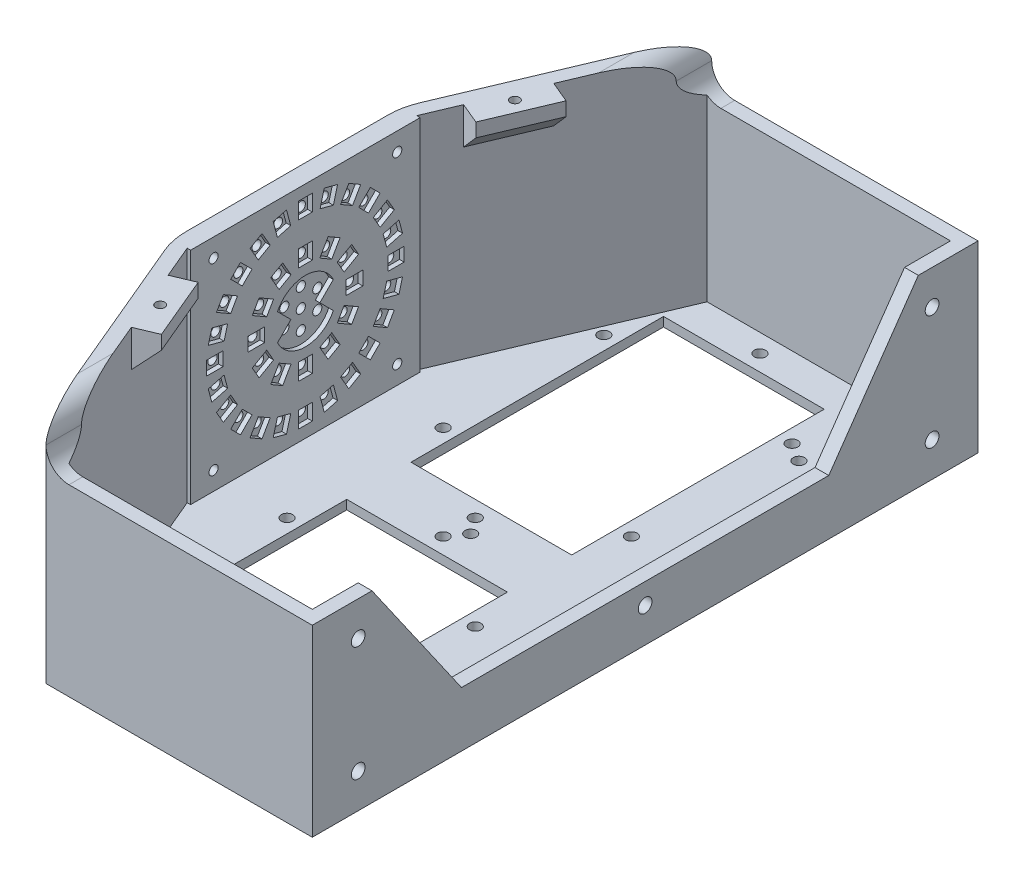
SolidWorks part; units mm, degrees
ref_plane "Спереди" through (0, 0, 0) normal (0, 0, 1) x (1, 0, 0)
ref_plane "Сверху" through (0, 0, 0) normal (0, 1, 0) x (1, 0, 0)
ref_plane "Справа" through (0, 0, 0) normal (1, 0, 0) x (0, 0, -1)
sketch "Эскиз1" plane through (0, 0, 0) normal (0, 1, 0) x (1, 0, 0)
  line L0 (0, 159.887) -> (0, 0) construction
  line L1 (0, 0) -> (281.7797, 0) construction
  line L2 (-95, -50) -> (-95, 50)
  line L3 (-55, -145) -> (55, -145)
  line L5 (-55, 145) -> (55, 145)
  line L6 (55, -145) -> (55, 145)
  line L7 (0, 145) -> (0, -145) construction
  line L8 (-435.8276, 0) -> (55, 0) construction
  line L9 (-95, 50) -> (-55, 145)
  line L10 (-95, -50) -> (-55, -145)
  point P10 (-95, 0)
  dimension "D1" = 290
  dimension "D2" = 110
  dimension "D3" = 100
  dimension "D4" = 150
extrude "Бобышка-Вытянуть1" add sketch "Эскиз1" along normal blind 4
sketch "Эскиз2" plane through (0, 0, 0) normal (0, 1, 0) x (1, 0, 0)
  line L1 (55, 145) -> (61, 145)
  line L2 (55, 145) -> (55, -145)
  line L3 (55, -145) -> (61, -145)
  line L4 (61, 145) -> (61, -145)
  dimension "D1" = 290
  dimension "D2" = 6
extrude "Бобышка-Вытянуть2" add sketch "Эскиз2" along normal blind 80
sketch "Эскиз17" plane through (0, 4, 0) normal (0, 1, 0) x (1, 0, 0)
  line L0 (-55, 145) -> (-95, 50)
  line L1 (-95, 50) -> (-95, -50)
  line L2 (-95, -50) -> (-55, -145)
  line L3 (-55, -145) -> (61, -145)
  line L4 (61, -145) -> (61, 145)
  line L5 (61, 145) -> (-55, 145)
extrude "Вытянуть-Тонкостенный1" add sketch "Эскиз17" along normal blind 96 thin thin type one direction reverse wall 6
sketch "Эскиз29" plane through (0, 100, 0) normal (0, 1, 0) x (1, 0, 0)
  line L1 (-95, 50) -> (-87, 50)
  line L2 (-95, 50) -> (-95, -50)
  line L3 (-95, -50) -> (-87, -50)
  line L4 (-87, 50) -> (-87, -50)
  dimension "D1" = 8
extrude "Бобышка-Вытянуть5" add sketch "Эскиз29" against normal blind 96
sketch "Эскиз20" plane through (-87, 0, 0) normal (1, 0, 0) x (0, 0, -1)
  line L0 (8.2314, 94.3113) -> (6.3873, 87.4288)
  line L1 (6.3, 52) -> (12.1612, 57.8612)
  line L10 (0, 0) -> (0, 100) construction
  line L12 (-48.7884, 52) -> (48.7884, 52) construction
  line L15 (-3, 95) -> (3, 95)
  line L16 (-3, 95) -> (-3, 87.8748)
  line L17 (-3, 87.8748) -> (3, 87.8748)
  line L18 (3, 95) -> (3, 87.8748)
  line L19 (0, 87.8748) -> (0, 95) construction
  line L20 (-3, 91.4374) -> (3, 91.4374) construction
  line L21 (8.2314, 94.3113) -> (14.027, 92.7584)
  line L22 (14.027, 92.7584) -> (12.1829, 85.8759)
  line L23 (6.3873, 87.4288) -> (12.1829, 85.8759)
  line L24 (18.9019, 90.7391) -> (15.3393, 84.5685)
  line L25 (18.9019, 90.7391) -> (24.0981, 87.7391)
  line L26 (24.0981, 87.7391) -> (20.5355, 81.5685)
  line L27 (15.3393, 84.5685) -> (20.5355, 81.5685)
  line L28 (28.2843, 84.5269) -> (23.246, 79.4886)
  line L29 (28.2843, 84.5269) -> (32.5269, 80.2843)
  line L30 (32.5269, 80.2843) -> (27.4886, 75.246)
  line L31 (23.246, 79.4886) -> (27.4886, 75.246)
  line L32 (35.7391, 76.0981) -> (29.5685, 72.5355)
  line L33 (35.7391, 76.0981) -> (38.7391, 70.9019)
  line L34 (38.7391, 70.9019) -> (32.5685, 67.3393)
  line L35 (29.5685, 72.5355) -> (32.5685, 67.3393)
  line L36 (40.7584, 66.027) -> (33.8759, 64.1829)
  line L37 (40.7584, 66.027) -> (42.3113, 60.2314)
  line L38 (42.3113, 60.2314) -> (35.4288, 58.3873)
  line L39 (33.8759, 64.1829) -> (35.4288, 58.3873)
  line L40 (43, 55) -> (35.8748, 55)
  line L41 (43, 55) -> (43, 49)
  line L42 (43, 49) -> (35.8748, 49)
  line L43 (35.8748, 55) -> (35.8748, 49)
  line L44 (42.3113, 43.7686) -> (35.4288, 45.6127)
  line L45 (42.3113, 43.7686) -> (40.7584, 37.973)
  line L46 (40.7584, 37.973) -> (33.8759, 39.8171)
  line L47 (35.4288, 45.6127) -> (33.8759, 39.8171)
  line L48 (38.7391, 33.0981) -> (32.5685, 36.6607)
  line L49 (38.7391, 33.0981) -> (35.7391, 27.9019)
  line L50 (35.7391, 27.9019) -> (29.5685, 31.4645)
  line L51 (32.5685, 36.6607) -> (29.5685, 31.4645)
  line L52 (32.5269, 23.7157) -> (27.4886, 28.754)
  line L53 (32.5269, 23.7157) -> (28.2843, 19.4731)
  line L54 (28.2843, 19.4731) -> (23.246, 24.5114)
  line L55 (27.4886, 28.754) -> (23.246, 24.5114)
  line L56 (24.0981, 16.2609) -> (20.5355, 22.4315)
  line L57 (24.0981, 16.2609) -> (18.9019, 13.2609)
  line L58 (18.9019, 13.2609) -> (15.3393, 19.4315)
  line L59 (20.5355, 22.4315) -> (15.3393, 19.4315)
  line L60 (14.027, 11.2416) -> (12.1829, 18.1241)
  line L61 (14.027, 11.2416) -> (8.2314, 9.6887)
  line L62 (8.2314, 9.6887) -> (6.3873, 16.5712)
  line L63 (12.1829, 18.1241) -> (6.3873, 16.5712)
  line L64 (3, 9) -> (3, 16.1252)
  line L65 (3, 9) -> (-3, 9)
  line L66 (-3, 9) -> (-3, 16.1252)
  line L67 (3, 16.1252) -> (-3, 16.1252)
  line L68 (-8.2314, 9.6887) -> (-6.3873, 16.5712)
  line L69 (-8.2314, 9.6887) -> (-14.027, 11.2416)
  line L70 (-14.027, 11.2416) -> (-12.1829, 18.1241)
  line L71 (-6.3873, 16.5712) -> (-12.1829, 18.1241)
  line L72 (-18.9019, 13.2609) -> (-15.3393, 19.4315)
  line L73 (-18.9019, 13.2609) -> (-24.0981, 16.2609)
  line L74 (-24.0981, 16.2609) -> (-20.5355, 22.4315)
  line L75 (-15.3393, 19.4315) -> (-20.5355, 22.4315)
  line L76 (-28.2843, 19.4731) -> (-23.246, 24.5114)
  line L77 (-28.2843, 19.4731) -> (-32.5269, 23.7157)
  line L78 (-32.5269, 23.7157) -> (-27.4886, 28.754)
  line L79 (-23.246, 24.5114) -> (-27.4886, 28.754)
  line L80 (-35.7391, 27.9019) -> (-29.5685, 31.4645)
  line L81 (-35.7391, 27.9019) -> (-38.7391, 33.0981)
  line L82 (-38.7391, 33.0981) -> (-32.5685, 36.6607)
  line L83 (-29.5685, 31.4645) -> (-32.5685, 36.6607)
  line L84 (-40.7584, 37.973) -> (-33.8759, 39.8171)
  line L85 (-40.7584, 37.973) -> (-42.3113, 43.7686)
  line L86 (-42.3113, 43.7686) -> (-35.4288, 45.6127)
  line L87 (-33.8759, 39.8171) -> (-35.4288, 45.6127)
  line L88 (-43, 49) -> (-35.8748, 49)
  line L89 (-43, 49) -> (-43, 55)
  line L90 (-43, 55) -> (-35.8748, 55)
  line L91 (-35.8748, 49) -> (-35.8748, 55)
  line L92 (-42.3113, 60.2314) -> (-35.4288, 58.3873)
  line L93 (-42.3113, 60.2314) -> (-40.7584, 66.027)
  line L94 (-40.7584, 66.027) -> (-33.8759, 64.1829)
  line L95 (-35.4288, 58.3873) -> (-33.8759, 64.1829)
  line L96 (-38.7391, 70.9019) -> (-32.5685, 67.3393)
  line L97 (-38.7391, 70.9019) -> (-35.7391, 76.0981)
  line L98 (-35.7391, 76.0981) -> (-29.5685, 72.5355)
  line L99 (-32.5685, 67.3393) -> (-29.5685, 72.5355)
  line L100 (-32.5269, 80.2843) -> (-27.4886, 75.246)
  line L101 (-32.5269, 80.2843) -> (-28.2843, 84.5269)
  line L102 (-28.2843, 84.5269) -> (-23.246, 79.4886)
  line L103 (-27.4886, 75.246) -> (-23.246, 79.4886)
  line L104 (-24.0981, 87.7391) -> (-20.5355, 81.5685)
  line L105 (-24.0981, 87.7391) -> (-18.9019, 90.7391)
  line L106 (-18.9019, 90.7391) -> (-15.3393, 84.5685)
  line L107 (-20.5355, 81.5685) -> (-15.3393, 84.5685)
  line L108 (-14.027, 92.7584) -> (-12.1829, 85.8759)
  line L109 (-14.027, 92.7584) -> (-8.2314, 94.3113)
  line L110 (-8.2314, 94.3113) -> (-6.3873, 87.4288)
  line L111 (-12.1829, 85.8759) -> (-6.3873, 87.4288)
  line L112 (6.276, 68.8704) -> (9.9019, 75.1506)
  line L113 (-3, 69.7482) -> (3, 69.7482)
  line L114 (-3, 69.7482) -> (-3, 77)
  line L115 (-3, 77) -> (3, 77)
  line L116 (3, 69.7482) -> (3, 77)
  line L117 (0, 77) -> (0, 69.7482) construction
  line L118 (-3, 73.3741) -> (3, 73.3741) construction
  line L119 (6.276, 68.8704) -> (11.4722, 65.8704)
  line L120 (11.4722, 65.8704) -> (15.0981, 72.1506)
  line L121 (9.9019, 75.1506) -> (15.0981, 72.1506)
  line L122 (13.8704, 63.4722) -> (20.1506, 67.0981)
  line L123 (13.8704, 63.4722) -> (16.8704, 58.276)
  line L124 (16.8704, 58.276) -> (23.1506, 61.9019)
  line L125 (20.1506, 67.0981) -> (23.1506, 61.9019)
  line L126 (17.7482, 55) -> (25, 55)
  line L127 (17.7482, 55) -> (17.7482, 49)
  line L128 (17.7482, 49) -> (25, 49)
  line L129 (25, 55) -> (25, 49)
  line L130 (16.8704, 45.724) -> (23.1506, 42.0981)
  line L131 (16.8704, 45.724) -> (13.8704, 40.5278)
  line L132 (13.8704, 40.5278) -> (20.1506, 36.9019)
  line L133 (23.1506, 42.0981) -> (20.1506, 36.9019)
  line L134 (11.4722, 38.1296) -> (15.0981, 31.8494)
  line L135 (11.4722, 38.1296) -> (6.276, 35.1296)
  line L136 (6.276, 35.1296) -> (9.9019, 28.8494)
  line L137 (15.0981, 31.8494) -> (9.9019, 28.8494)
  line L138 (3, 34.2518) -> (3, 27)
  line L139 (3, 34.2518) -> (-3, 34.2518)
  line L140 (-3, 34.2518) -> (-3, 27)
  line L141 (3, 27) -> (-3, 27)
  line L142 (-6.276, 35.1296) -> (-9.9019, 28.8494)
  line L143 (-6.276, 35.1296) -> (-11.4722, 38.1296)
  line L144 (-11.4722, 38.1296) -> (-15.0981, 31.8494)
  line L145 (-9.9019, 28.8494) -> (-15.0981, 31.8494)
  line L146 (-13.8704, 40.5278) -> (-20.1506, 36.9019)
  line L147 (-13.8704, 40.5278) -> (-16.8704, 45.724)
  line L148 (-16.8704, 45.724) -> (-23.1506, 42.0981)
  line L149 (-20.1506, 36.9019) -> (-23.1506, 42.0981)
  line L150 (-17.7482, 49) -> (-25, 49)
  line L151 (-17.7482, 49) -> (-17.7482, 55)
  line L152 (-17.7482, 55) -> (-25, 55)
  line L153 (-25, 49) -> (-25, 55)
  line L154 (-16.8704, 58.276) -> (-23.1506, 61.9019)
  line L155 (-16.8704, 58.276) -> (-13.8704, 63.4722)
  line L156 (-13.8704, 63.4722) -> (-20.1506, 67.0981)
  line L157 (-23.1506, 61.9019) -> (-20.1506, 67.0981)
  line L158 (-11.4722, 65.8704) -> (-15.0981, 72.1506)
  line L159 (-11.4722, 65.8704) -> (-6.276, 68.8704)
  line L160 (-6.276, 68.8704) -> (-9.9019, 75.1506)
  line L161 (-15.0981, 72.1506) -> (-9.9019, 75.1506)
  line L162 (6.3, 52) -> (12.1612, 46.1388)
  line L163 (-6.3, 52) -> (-12.1612, 57.8612)
  line L164 (-6.3, 52) -> (-12.1612, 46.1388)
  circle A0 centre (0, 52) radius 36 construction
  circle A1 centre (0, 52) radius 43 construction
  circle A3 centre (0, 52) radius 25 construction
  circle A4 centre (0, 52) radius 18 construction
  circle A5 centre (0, 52) radius 13.5 construction
  arc A6 (-12.1612, 57.8612) -> (12.1612, 57.8612) centre (0, 52) cw
  arc A7 (-12.1612, 46.1388) -> (12.1612, 46.1388) centre (0, 52) ccw
  point P15 (0, 91.4374)
  point P21 (0, 73.3741)
  point P112 (0, 52)
  point P163 (0, 52)
  dimension "D1" = 72
  dimension "D2" = 86
  dimension "D3" = 50
  dimension "D5" = 36
  dimension "D7" = 27
  dimension "D4" = 6
  dimension "D6" = 6
  dimension "D8" = 6.3
  dimension "D9" = 90
extrude "Вырез-Вытянуть7" cut sketch "Эскиз20" against normal blind 2
sketch "Эскиз16" plane through (61, 0, 0) normal (1, 0, 0) x (0, 0, -1)
  line L0 (0, 111.0778) -> (0, 40) construction
  line L1 (0, 40) -> (205.7417, 40) construction
  line L2 (-145, 0) -> (145, 0) construction
  circle A0 centre (0, 65) radius 3
  circle A1 centre (0, 15) radius 3
  circle A2 centre (125, 65) radius 3
  circle A3 centre (-125, 65) radius 3
  circle A4 centre (-125, 15) radius 3
  circle A5 centre (125, 15) radius 3
  dimension "D2" = 6
  dimension "D3" = 25
  dimension "D4" = 125
  dimension "D1" = 40
extrude "Вырез-Вытянуть6" cut sketch "Эскиз16" against normal blind 20
sketch "Эскиз21" plane through (-87, 0, 0) normal (1, 0, 0) x (0, 0, -1)
  line L0 (48.7884, 52) -> (-48.7884, 52) construction
  line L3 (0, 100) -> (0, 0) construction
  circle A0 centre (0, 52) radius 38.5 construction
  circle A1 centre (0, 90.5) radius 2
  circle A2 centre (9.9645, 89.1881) radius 2
  circle A3 centre (19.25, 85.342) radius 2
  circle A4 centre (27.2236, 79.2236) radius 2
  circle A5 centre (33.342, 71.25) radius 2
  circle A6 centre (37.1881, 61.9645) radius 2
  circle A7 centre (38.5, 52) radius 2
  circle A8 centre (37.1881, 42.0355) radius 2
  circle A9 centre (33.342, 32.75) radius 2
  circle A10 centre (27.2236, 24.7764) radius 2
  circle A11 centre (19.25, 18.658) radius 2
  circle A12 centre (9.9645, 14.8119) radius 2
  circle A13 centre (0, 13.5) radius 2
  circle A14 centre (-9.9645, 14.8119) radius 2
  circle A15 centre (-19.25, 18.658) radius 2
  circle A16 centre (-27.2236, 24.7764) radius 2
  circle A17 centre (-33.342, 32.75) radius 2
  circle A18 centre (-37.1881, 42.0355) radius 2
  circle A19 centre (-38.5, 52) radius 2
  circle A20 centre (-37.1881, 61.9645) radius 2
  circle A21 centre (-33.342, 71.25) radius 2
  circle A22 centre (-27.2236, 79.2236) radius 2
  circle A23 centre (-19.25, 85.342) radius 2
  circle A24 centre (-9.9645, 89.1881) radius 2
  circle A25 centre (0, 52) radius 21 construction
  circle A26 centre (0, 73) radius 2
  circle A27 centre (10.5, 70.1865) radius 2
  circle A28 centre (18.1865, 62.5) radius 2
  circle A29 centre (21, 52) radius 2
  circle A30 centre (18.1865, 41.5) radius 2
  circle A31 centre (10.5, 33.8135) radius 2
  circle A32 centre (0, 31) radius 2
  circle A33 centre (-10.5, 33.8135) radius 2
  circle A34 centre (-18.1865, 41.5) radius 2
  circle A35 centre (-21, 52) radius 2
  circle A36 centre (-18.1865, 62.5) radius 2
  circle A37 centre (-10.5, 70.1865) radius 2
  circle A38 centre (0, 52) radius 8.3 construction
  circle A39 centre (0, 60.3) radius 2
  circle A40 centre (7.188, 56.15) radius 2
  circle A41 centre (7.188, 47.85) radius 2
  circle A42 centre (0, 43.7) radius 2
  circle A43 centre (-7.188, 47.85) radius 2
  circle A44 centre (-7.188, 56.15) radius 2
  circle A45 centre (0, 52) radius 2
  point P64 (0, 52)
  point P90 (0, 52)
  point P104 (0, 52)
  dimension "D1" = 77
  dimension "D2" = 4
  dimension "D3" = 42
  dimension "D4" = 4
  dimension "D5" = 16.6
  dimension "D6" = 4
extrude "Отверстия под LED" cut sketch "Эскиз21" against normal blind 10
sketch "Эскиз22" plane through (0, 100, 0) normal (0, 1, 0) x (1, 0, 0)
  line L1 (61, 145) -> (-55, 145)
  line L2 (61, 145) -> (61, -145)
  line L3 (61, -145) -> (-55, -145)
  line L4 (-55, 145) -> (-55, -145)
extrude "Вырез-Вытянуть9" cut sketch "Эскиз22" against normal blind 20
fillet "Скругление2" radius 10 4 edges at (-55, 100, -137.2692) (-55, 100, 137.2692) (-55, 80, -137.2692) (-55, 80, 137.2692)
fillet "Скругление3" radius 30 2 edges at (-95, 50, 50) (-95, 50, -50)
sketch "Эскиз23" plane through (-93.0467, 0, -39.1775) normal (0.9216, 0, 0.3881) x (0.3881, 0, -0.9216)
  line L0 (72.2746, 100) -> (11.7427, 100) construction
  line L1 (27.3208, 100) -> (57.3208, 100)
  line L2 (27.3208, 100) -> (27.3208, 94)
  line L3 (27.3208, 94) -> (57.3208, 94)
  line L4 (57.3208, 100) -> (57.3208, 94)
  line L6 (12.3208, 4) -> (12.3208, 100) construction
  dimension "D1" = 30
  dimension "D2" = 6
  dimension "D3" = 15
extrude "Бобышка-Вытянуть3" add sketch "Эскиз23" along normal blind 10
sketch "Эскиз24" plane through (-93.0467, 0, 39.1775) normal (0.9216, 0, -0.3881) x (-0.3881, 0, -0.9216)
  line L0 (-11.7427, 100) -> (-72.2746, 100) construction
  line L1 (-27.3208, 100) -> (-57.3208, 100)
  line L2 (-27.3208, 100) -> (-27.3208, 94)
  line L3 (-27.3208, 94) -> (-57.3208, 94)
  line L4 (-57.3208, 100) -> (-57.3208, 94)
  line L6 (-12.3208, 4) -> (-12.3208, 100) construction
  dimension "D1" = 30
  dimension "D2" = 6
  dimension "D3" = 15
extrude "Бобышка-Вытянуть4" add sketch "Эскиз24" along normal blind 10
chamfer "Фаска1" distance 10 angle 45 2 edges at (-76.6238, 94, -78.1819) (-76.6238, 94, 78.1819)
sketch "Эскиз27" plane through (61, 0, 0) normal (1, 0, 0) x (0, 0, -1)
  line L0 (-80, 24) -> (80, 24)
  line L1 (80, 24) -> (119, 80)
  line L2 (-145, 80) -> (145, 80) construction
  line L3 (119, 80) -> (-119, 80)
  line L4 (0, 118.8906) -> (0, 0) construction
  line L5 (-80, 24) -> (-119, 80)
  line L6 (-145, 0) -> (145, 0) construction
  line L7 (145, 80) -> (145, 0) construction
  point P10 (0, 80)
  point P11 (0, 24)
  dimension "D1" = 160
  dimension "D2" = 24
  dimension "D3" = 26
extrude "Вырез-Вытянуть10" cut sketch "Эскиз27" against normal blind 10
chamfer "Фаска2" distance 2 angle 45 24 edges at (-95, 71.25, 31.342) (-95, 61.9645, 35.1881) (-95, 52, 36.5) (-95, 42.0355, 35.1881) (-95, 32.75, 31.342) (-95, 24.7764, 25.2236) (-95, 18.658, 17.25) (-95, 14.8119, 7.9645) (-95, 13.5, -2) (-95, 14.8119, -11.9645) (-95, 18.658, -21.25) (-95, 24.7764, -29.2236) (-95, 32.75, -35.342) (-95, 42.0355, -39.1881) (-95, 52, -40.5) (-95, 61.9645, -39.1881) (-95, 71.25, -35.342) (-95, 79.2236, -29.2236) (-95, 85.342, -21.25) (-95, 89.1881, -11.9645) (-95, 90.5, -2) (-95, 79.2236, 25.2236) (-95, 85.342, 17.25) (-95, 89.1881, 7.9645)
sketch "Эскиз30" plane through (-87, 0, 0) normal (1, 0, 0) x (0, 0, -1)
  line L1 (-40, 12) -> (40, 12) construction
  line L2 (-40, 12) -> (-40, 92) construction
  line L3 (-40, 92) -> (40, 92) construction
  line L4 (40, 12) -> (40, 92) construction
  line L5 (0, 92) -> (0, 12) construction
  line L6 (-40, 52) -> (40, 52) construction
  circle A0 centre (-40, 92) radius 2
  circle A1 centre (40, 92) radius 2
  circle A2 centre (-40, 12) radius 2
  circle A3 centre (40, 12) radius 2
  point P0 (0, 52)
  dimension "D1" = 80
  dimension "D2" = 80
extrude "Вырез-Вытянуть11" cut sketch "Эскиз30" against normal blind 7
sketch "Эскиз32" plane through (0, 100, 0) normal (0, 1, 0) x (1, 0, 0)
  line L0 (-73, 139.8441) -> (-73, -154.1375) construction
  line L1 (-95, 43.9418) -> (-95, -43.9418) construction
  line L2 (0, 0) -> (-175.2904, 0) construction
  circle A0 centre (-73, 77.2619) radius 2
  circle A1 centre (-73, -77.2619) radius 2
  dimension "D2" = 77.2619
  dimension "D1" = 22
extrude "Вырез-Вытянуть13" cut sketch "Эскиз32" against normal blind 7
chamfer "Фаска3" distance 2 angle 45 7 edges at (-95, 47.85, 5.188) (-95, 43.7, -2) (-95, 47.85, -9.188) (-95, 56.15, -9.188) (-95, 52, -2) (-95, 56.15, 5.188) (-95, 60.3, -2)
sketch "Эскиз31" plane through (0, 100, 0) normal (0, 1, 0) x (1, 0, 0)
  line L1 (-70.4141, 145) -> (61, 145)
  line L2 (-70.4141, 145) -> (-70.4141, -145)
  line L3 (-70.4141, -145) -> (61, -145)
  line L4 (61, 145) -> (61, -145)
extrude "Вырез-Вытянуть12" [suppressed] cut sketch "Эскиз31" against normal blind 150
sketch "Эскиз33" plane through (0, 4, 0) normal (0, 1, 0) x (1, 0, 0)
  line L0 (-55, 124) -> (15, 124)
  line L1 (15, 124) -> (15, 14)
  line L2 (15, 14) -> (-55, 14)
  line L3 (-55, 14) -> (-55, 124)
  line L4 (0, 0) -> (-147.4761, 0) construction
  line L5 (55, 119) -> (55, 139) construction
  line L6 (55, 139) -> (-51.0161, 139) construction
  line L7 (15, -14) -> (-55, -14)
  line L8 (15, -124) -> (15, -14)
  line L9 (-55, -124) -> (15, -124)
  line L10 (-55, -14) -> (-55, -124)
  dimension "D1" = 40
  dimension "D2" = 70
  dimension "D3" = 110
  dimension "D4" = 15
extrude "Вырез-Вытянуть14" cut sketch "Эскиз33" against normal blind 10
sketch "Эскиз34" plane through (0, 4, 0) normal (0, 1, 0) x (1, 0, 0)
  line L0 (0, 0) -> (232.0731, 0) construction
  line L1 (-20, 157.0562) -> (-20, -124) construction
  line L3 (-55, -124) -> (15, -124) construction
  line L4 (55, 139) -> (-51.0161, 139) construction
  line L5 (-55, 69) -> (15, 69) construction
  line L6 (-55, 124) -> (-55, 14) construction
  line L7 (15, 14) -> (15, 124) construction
  line L8 (-55, -69) -> (15, -69) construction
  line L9 (-20, -157.0562) -> (-20, 124) construction
  line L10 (15, 124) -> (-55, 124) construction
  line L11 (55, -139) -> (55, 139) construction
  line L12 (-55, -69) -> (15, -69) construction
  circle A0 centre (-20, 131) radius 2.5
  circle A1 centre (21, 104) radius 2.5
  circle A3 centre (-61, 104) radius 2.5
  circle A4 centre (-61, 34) radius 2.5
  circle A5 centre (21, 34) radius 2.5
  circle A6 centre (21, -34) radius 2.5
  circle A7 centre (-61, -34) radius 2.5
  circle A8 centre (-61, -104) radius 2.5
  circle A9 centre (21, -104) radius 2.5
  circle A10 centre (-20, -131) radius 2.5
  circle A11 centre (-20, 7) radius 2.5
  circle A12 centre (-20, -7) radius 2.5
  circle A13 centre (29, 99) radius 2.5
  circle A14 centre (29, -99) radius 2.5
  circle A15 centre (-15, 0) radius 2.5
  dimension "D1" = 8
  dimension "D2" = 6
  dimension "D6" = 70
  dimension "D3" = 20
  dimension "D4" = 26
  dimension "D5" = 40
extrude "Вырез-Вытянуть15" cut sketch "Эскиз34" against normal blind 10
chamfer "Фаска4" distance 2 angle 45 12 edges at (-95, 52, 19) (-95, 41.5, 16.1865) (-95, 33.8135, 8.5) (-95, 31, -2) (-95, 33.8135, -12.5) (-95, 41.5, -20.1865) (-95, 52, -23) (-95, 62.5, -20.1865) (-95, 70.1865, -12.5) (-95, 73, -2) (-95, 70.1865, 8.5) (-95, 62.5, 16.1865)
